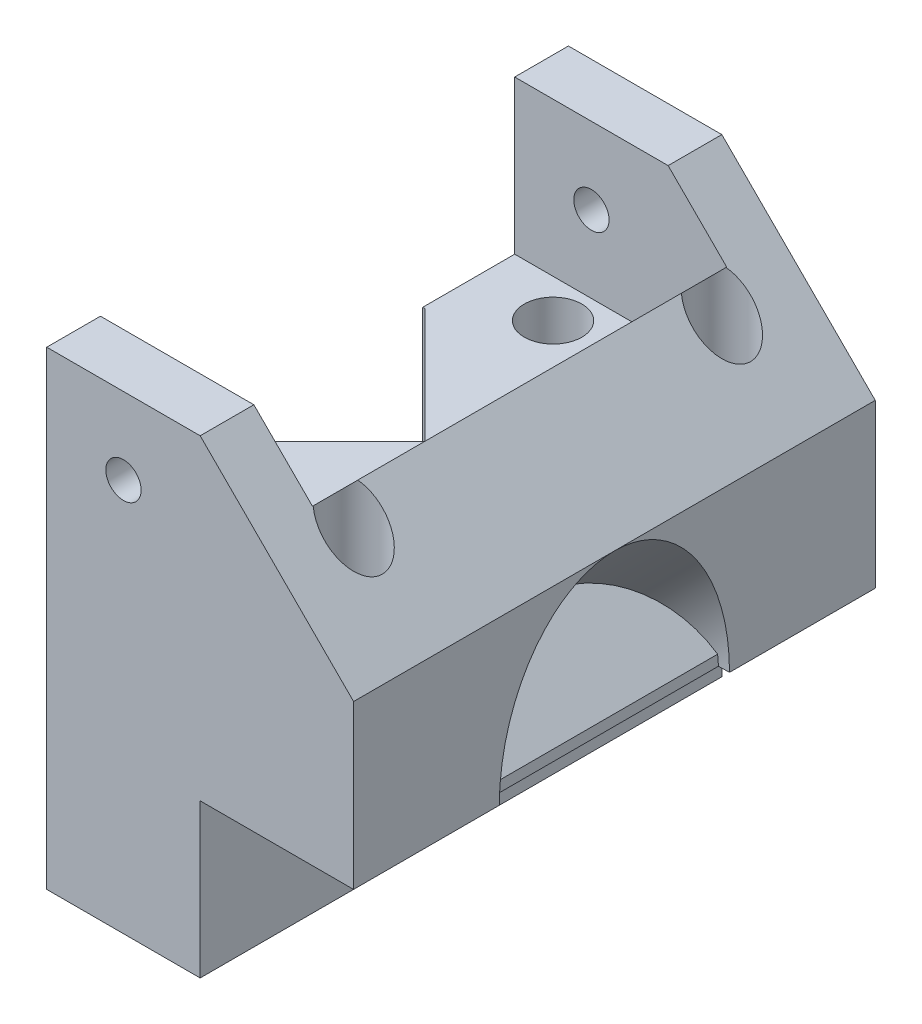
SolidWorks part; units mm, degrees
ref_plane "Front" through (0, 0, 0) normal (0, 0, 1) x (1, 0, 0)
ref_plane "Top" through (0, 0, 0) normal (0, 1, 0) x (1, 0, 0)
ref_plane "Right" through (0, 0, 0) normal (1, 0, 0) x (0, 0, -1)
sketch "Skizze1" plane through (0, 0, 0) normal (0, 0, 1) x (1, 0, 0)
  line L0 (0, 200) -> (0, 0) construction
  line L1 (0, 0) -> (20, 0)
  line L5 (40, 41.2132) -> (20, 61.2132)
  line L6 (20, 200) -> (20, 0) construction
  line L7 (241.5254, 242.7386) -> (29.3934, 30.6066) construction
  line L9 (0, 61.2132) -> (20, 61.2132)
  line L10 (0, 61.2132) -> (0, 0)
  line L11 (20, 0) -> (20, 20)
  line L12 (20, 20) -> (40, 20)
  line L18 (40, 20) -> (40, 41.2132)
extrude "Aufsatz-Linear austragen1" add sketch "Skizze1" against normal up to surface (68 mm away)
sketch "Skizze4" plane through (30, 30, 0) normal (-0.7071, -0.7071, 0) x (0, 0, 1)
  circle A0 centre (-34, -14.1421) radius 15
  dimension "D1" = 30
extrude "Schnitt-Linear austragen1" cut sketch "Skizze4" against normal blind 20
sketch "Skizze9" plane through (0, 61.2132, 0) normal (0, 1, 0) x (1, 0, 0)
  line L0 (0, 61) -> (27.6355, 61)
  line L1 (0, 68) -> (0, 0) construction
  line L2 (0, 34) -> (34.3694, 34) construction
  line L3 (0, 7) -> (27.6355, 7)
  line L4 (0, 7) -> (0, 61)
  line L5 (27.6355, 61) -> (27.6355, 7)
  line L6 (20, 68) -> (0, 68) construction
  dimension "D1" = 7
extrude "Schnitt-Linear austragen6" cut sketch "Skizze9" against normal blind 20
ref_plane "Ebene1" through (0, 7, 0) normal (0, -1, 0) x (-1, 0, 0)
sketch "Skizze5" plane through (0, 7, 0) normal (0, -1, 0) x (-1, 0, 0)
  line L0 (-10, 68) -> (-10, 0) construction
  line L1 (0, 68) -> (-20, 68) construction
  line L2 (0, 0) -> (-20, 0) construction
  line L3 (0, 34) -> (29.1764, 34) construction
  line L4 (0, 68) -> (0, 0) construction
  circle A0 centre (-10, 56) radius 2.3
  circle A2 centre (-10, 12) radius 2.3
  dimension "D1" = 4.6
  dimension "D2" = 12
extrude "Schnitt-Linear austragen2" cut sketch "Skizze5" along normal blind 20
sketch "Skizze6" plane through (0, 7, 0) normal (0, -1, 0) x (-1, 0, 0)
  circle A0 centre (-10, 56) radius 3.75
  circle A1 centre (-10, 12) radius 3.75
  dimension "D1" = 7.5
  dimension "D2" = 7.5
extrude "Schnitt-Linear austragen3" cut sketch "Skizze6" against normal through all
ref_plane "Ebene2" through (0, 27, 0) normal (0, -1, 0) x (-1, 0, 0)
sketch "Skizze7" plane through (0, 27, 0) normal (0, -1, 0) x (-1, 0, 0)
  line L0 (-30, 68) -> (-30, 0) construction
  line L1 (-20, 68) -> (-40, 68) construction
  line L2 (-20, 0) -> (-40, 0) construction
  line L3 (-30, 34) -> (12.5207, 34) construction
  circle A0 centre (-30, 58) radius 2.3
  circle A1 centre (-30, 10) radius 2.3
  dimension "D1" = 4.6
  dimension "D2" = 10
extrude "Schnitt-Linear austragen4" cut sketch "Skizze7" along normal blind 20
sketch "Skizze8" plane through (0, 27, 0) normal (0, -1, 0) x (-1, 0, 0)
  circle A0 centre (-30, 58) radius 3.75
  circle A1 centre (-30, 10) radius 3.75
  dimension "D1" = 7.5
extrude "Schnitt-Linear austragen5" cut sketch "Skizze8" against normal through all
chamfer "Fase1" distance 12.36 angle 45 1 edges at (27.6355, 41.2132, -34)
sketch "Skizze10" plane through (0, 41.2132, 0) normal (0, 1, 0) x (1, 0, 0)
  line L0 (0, 49) -> (15.2755, 49)
  line L1 (0, 61) -> (0, 7) construction
  line L2 (15.2755, 7) -> (15.2755, 61) construction
  line L3 (0, 34) -> (8.7391, 34) construction
  line L4 (15.2755, 49) -> (15.2755, 19)
  line L5 (0, 49) -> (0, 19)
  line L6 (0, 19) -> (15.2755, 19)
  point P12 (15.2755, 34)
  dimension "D1" = 30
extrude "Schnitt-Linear austragen7" cut sketch "Skizze10" against normal offset from surface (31.2132 mm away) 10 up to face at (12.3, 0, -56)
chamfer "Fase2" distance 15 angle 45 2 edges at (15.2755, 25.6066, -19) (15.2755, 25.6066, -49)
sketch "Skizze12" plane through (0, 0, -68) normal (0, 0, -1) x (-1, 0, 0)
  line L0 (-10, 61.2132) -> (-10, 14.2762) construction
  line L1 (-20, 61.2132) -> (0, 61.2132) construction
  line L2 (0, 61.2132) -> (0, 0) construction
  circle A0 centre (-10, 51.2132) radius 2.3
  dimension "D2" = 4.6
  dimension "D1" = 10
  dimension "D3" = 10
extrude "Schnitt-Linear austragen8" cut sketch "Skizze12" against normal through all
chamfer "Fase3" distance 2 angle 45 1 edges at (40, 20, -34) first distance on face at (34.6967, 25.3033, -34)
